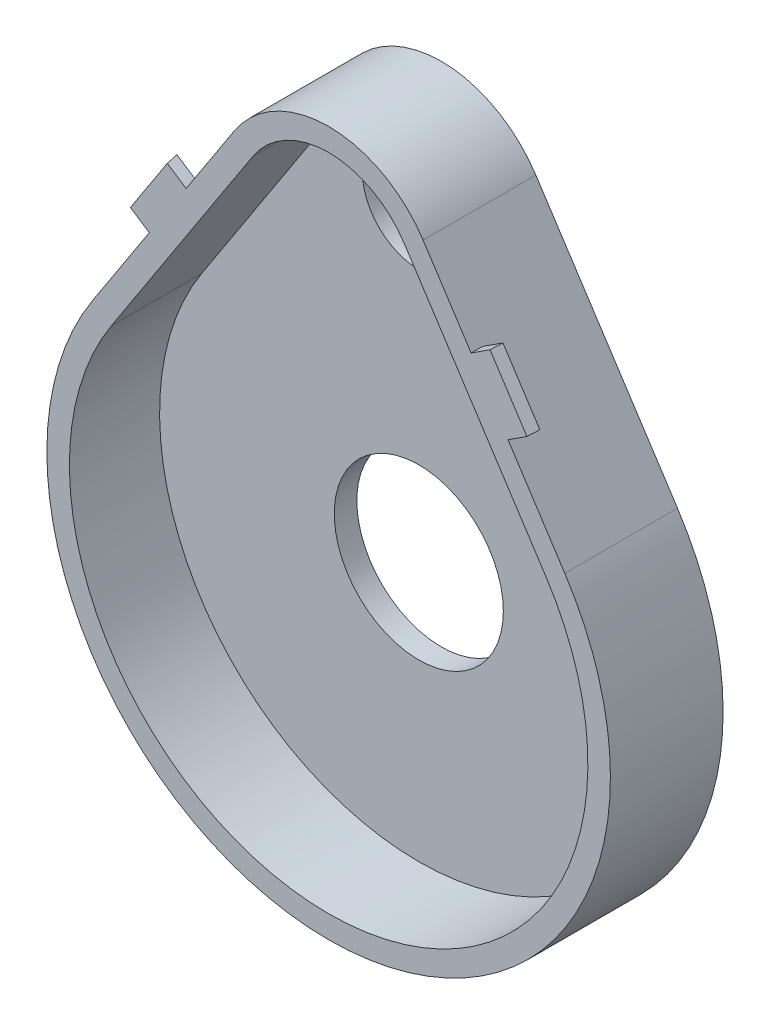
SolidWorks part; units mm, degrees
ref_plane "Front Plane" through (0, 0, 0) normal (1, 0, 0) x (0, 1, 0)
ref_plane "Top Plane" through (0, 0, 0) normal (0, 0, 1) x (0, 1, 0)
ref_plane "Right Plane" through (0, 0, 0) normal (0, 1, 0) x (-1, 0, 0)
sketch "Sketch2" plane through (0, 0, 0) normal (0, 0, 1) x (0, 1, 0)
  line L0 (8.6591, -13.3055) -> (20.9261, -5.3222)
  line L1 (0, 0) -> (20.6375, 0) construction
  line L2 (8.6591, 13.3055) -> (20.9261, 5.3222)
  circle A4 centre (0, 0) radius 4.7625
  circle A5 centre (17.4625, 0) radius 3.175
  arc A6 (8.6591, 13.3055) -> (8.6591, -13.3055) centre (0, 0) ccw
  arc A7 (20.9261, -5.3222) -> (20.9261, 5.3222) centre (17.4625, 0) ccw
  dimension "D1" = 9.525
  dimension "D2" = 6.35
  dimension "D3" = 17.4625
  dimension "D4" = 31.75
  dimension "D5" = 12.7
extrude "Boss-Extrude2" add sketch "Sketch2" along normal blind 6.35 contours A6 L0 A7 L2
shell "Shell3" thickness 1.27 removed face at (0, 9.3807, 6.35)
extrude "Cut-Extrude2" cut sketch "Sketch2<7>" along normal through all contours A5 | A4
sketch "Sketch2<7>" plane through (0, 0, 0) normal (0, 0, 1) x (0, 1, 0) same geometry as "Sketch2"
ref_plane "Plane1" through (0, 0, 5.715) normal (0, 0, 1) x (0, -1, 0)
sketch "Sketch6" plane through (0, 0, 5.715) normal (0, 0, 1) x (0, -1, 0)
  line L0 (-16.7698, 8.0271) -> (-17.4625, 9.0916)
  line L1 (-8.6591, 13.3055) -> (-20.9261, 5.3222) construction
  line L2 (-17.4625, 9.0916) -> (-14.2692, 11.1697)
  line L3 (-14.2692, 11.1697) -> (-13.5765, 10.1053)
  line L4 (-17.4625, 0) -> (0, 0) construction
  line L5 (-14.2692, -11.1697) -> (-13.5765, -10.1053)
  line L6 (-16.7698, -8.0271) -> (-17.4625, -9.0916)
  line L7 (-17.4625, -9.0916) -> (-14.2692, -11.1697)
  line L8 (-16.7698, 8.0271) -> (-13.5765, 10.1053)
  line L9 (-16.7698, -8.0271) -> (-13.5765, -10.1053)
  dimension "D1" = 3.81
  dimension "D2" = 1.27
extrude "Boss-Extrude3" add sketch "Sketch6" along normal up to surface (0.635 mm away) up to face at (0, 9.3807, 6.35)
draft "Draft2" type of draft neutral plane draft angle 10 faces to draft 2 face at (10.1306, 15.8658, 6.0325) face at (-10.1306, 15.8658, 6.0325) neutral plane through (0, 17.4625, 6.35) neutral plane normal (0, 0, 1) parameters "D1"=10
